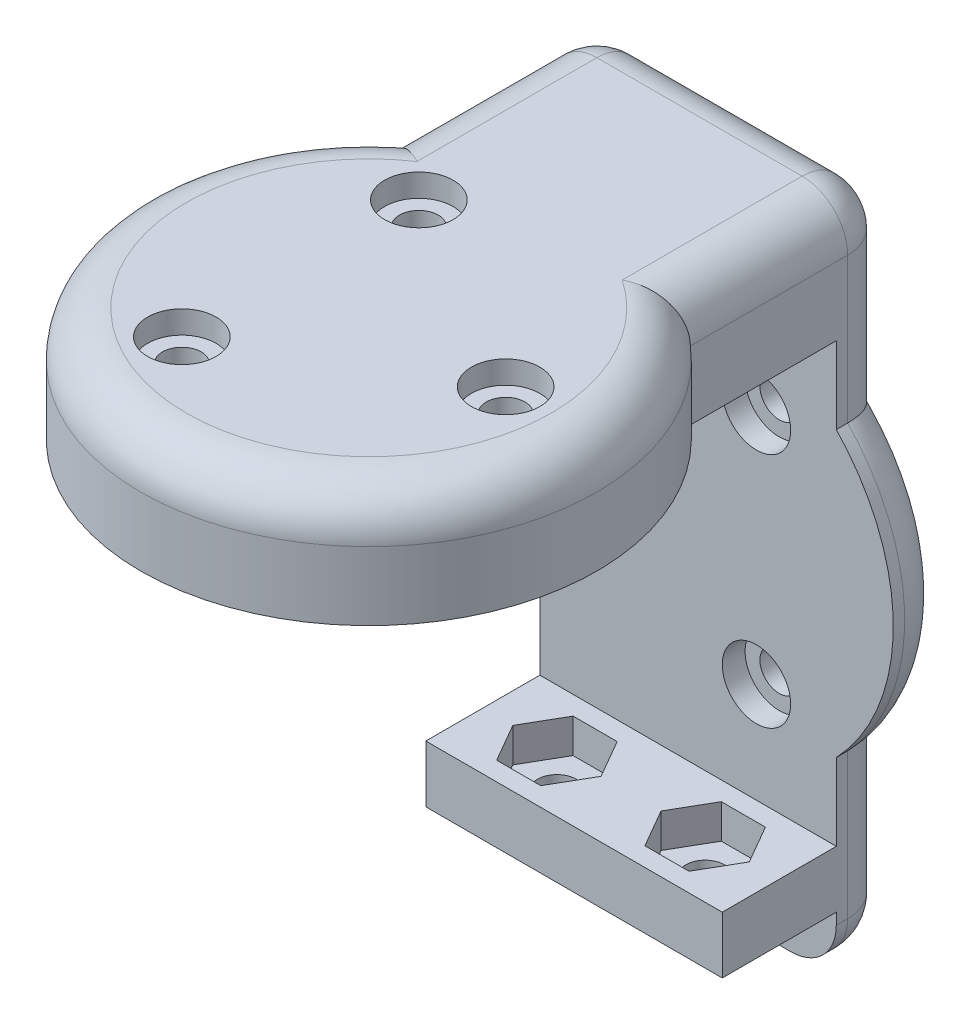
SolidWorks part; units mm, degrees
ref_plane "前视基准面" through (0, 0, 0) normal (0, 0, 1) x (1, 0, 0)
ref_plane "上视基准面" through (0, 0, 0) normal (0, 1, 0) x (1, 0, 0)
ref_plane "右视基准面" through (0, 0, 0) normal (1, 0, 0) x (0, 0, -1)
sketch "草图1" plane through (0, 0, 0) normal (0, 0, 1) x (1, 0, 0)
  line L0 (-6.5, -6.2249) -> (-6.5, -9.6)
  line L5 (-6.5, 9.6) -> (6.5, 9.6)
  line L6 (-6.5, 9.6) -> (-6.5, 6.2249)
  line L7 (-6.5, -9.6) -> (6.5, -9.6)
  line L8 (6.5, 9.6) -> (6.5, 6.2249)
  line L9 (6.5, -6.2249) -> (6.5, -9.6)
  arc A0 (-6.5, 6.2249) -> (-6.5, -6.2249) centre (0, 0) ccw
  arc A1 (6.5, -6.2249) -> (6.5, 6.2249) centre (0, 0) ccw
  point P0 (0, 0)
  point P1 (0, 0)
  point P20 (-2.9403, 5.0928)
  point P24 (-2.9182, -5.2425)
extrude "凸台-拉伸1" add sketch "草图1" along normal blind 2.5 contours L5 L8 A1 L9 L7 L0 A0 L6
ref_plane "基准面4" through (0, 0, -10) normal (0, 0, -1) x (-1, 0, 0)
sketch "草图2" plane through (0, 0, -10) normal (0, 0, -1) x (-1, 0, 0)
  line L1 (6.5, -9.6) -> (-6.5, -9.6)
  line L2 (6.5, -9.6) -> (6.5, -12.1)
  line L3 (6.5, -12.1) -> (-6.5, -12.1)
  line L4 (-6.5, -9.6) -> (-6.5, -12.1)
  circle A8 centre (6, 0) radius 0.85
  circle A9 centre (6, 0) radius 1.5
  circle A10 centre (-3, 5.1962) radius 0.85
  circle A11 centre (-3, 5.1962) radius 1.5
  circle A12 centre (-3, -5.1962) radius 0.85
  circle A13 centre (-3, -5.1962) radius 1.5
extrude "切除-拉伸1" cut sketch "草图2" against normal blind 16.5 contours A12 | A8 | A10
extrude "切除-拉伸2" cut sketch "草图2<3>" along normal blind 1 from surface contours A13 | A9 | A11 starting at face at (3.85, -5.1962, 2.5)
sketch "草图2<3>" plane through (0, 0, -10) normal (0, 0, -1) x (-1, 0, 0) same geometry as "草图2"
sketch "草图3" plane through (0, 0, 0) normal (0, 1, 0) x (1, 0, 0)
  line L1 (6.5, 0) -> (-6.5, 0)
  line L2 (6.5, 0) -> (6.5, -8.9007)
  line L4 (-6.5, 0) -> (-6.5, -8.9007)
  arc A0 (-6.5, -8.9007) -> (6.5, -8.9007) centre (0, -16.5) ccw
extrude "凸台-拉伸2" add sketch "草图3" along normal blind 5 from surface starting at face at (0, 9.6, 1.25)
ref_plane "基准面5" through (0, 24.6, 0) normal (0, 1, 0) x (1, 0, 0)
sketch "草图4" plane through (0, 24.6, 0) normal (0, 1, 0) x (1, 0, 0)
  line L16 (-6.5, 0) -> (6.5, 0)
  line L17 (-6.5, 0) -> (-6.5, -2.5)
  line L18 (-6.5, -2.5) -> (6.5, -2.5)
  line L19 (6.5, 0) -> (6.5, -2.5)
  line L20 (2.2829, -6.675) -> (1.3159, -5)
  line L21 (-1.3159, -5) -> (-2.2829, -3.325)
  line L22 (-2.2829, -3.325) -> (-4.2171, -3.325)
  line L23 (-4.2171, -3.325) -> (-5.1841, -5)
  line L24 (-5.1841, -5) -> (-4.2171, -6.675)
  line L25 (-4.2171, -6.675) -> (-2.2829, -6.675)
  line L26 (-2.2829, -6.675) -> (-1.3159, -5)
  line L27 (4.2171, -6.675) -> (2.2829, -6.675)
  line L28 (5.1841, -5) -> (4.2171, -6.675)
  line L29 (4.2171, -3.325) -> (5.1841, -5)
  line L30 (2.2829, -3.325) -> (4.2171, -3.325)
  line L31 (1.3159, -5) -> (2.2829, -3.325)
  circle A10 centre (0, -16.5) radius 8.5
  circle A11 centre (6, -16.5) radius 0.85
  circle A14 centre (6, -16.5) radius 1.5
  circle A15 centre (-3, -11.3038) radius 0.85
  circle A16 centre (-3, -11.3038) radius 1.5
  circle A17 centre (-3, -21.6962) radius 0.85
  circle A18 centre (-3, -21.6962) radius 1.5
  circle A19 centre (0, -16.5) radius 6.1
  circle A20 centre (-3.25, -5) radius 0.85
  circle A21 centre (-3.25, -5) radius 1.5
  circle A22 centre (-3.25, -5) radius 1.675 construction
  circle A23 centre (3.25, -5) radius 1.675 construction
  circle A24 centre (3.25, -5) radius 1.5
  circle A25 centre (3.25, -5) radius 0.85
  point P0 (0, -16.5)
extrude "切除-拉伸3" cut sketch "草图4" against normal blind 5 from surface contours A17 | A11 | A15 starting at face at (0, 14.6, 8.8502)
extrude "切除-拉伸4" cut sketch "草图4<3>" against normal blind 1 from surface contours A18 | A16 | A14 starting at face at (-3.85, 14.6, 21.6962)
sketch "草图4<3>" plane through (0, 24.6, 0) normal (0, 1, 0) x (1, 0, 0) same geometry as "草图4"
extrude "切除-拉伸5" cut sketch "草图4<4>" along normal blind 2.5 from surface contours A10 starting at face at (-3.85, 9.6, 21.6962)
sketch "草图4<4>" plane through (0, 24.6, 0) normal (0, 1, 0) x (1, 0, 0) same geometry as "草图4"
extrude "凸台-拉伸3" add sketch "草图4<5>" against normal blind 5 from surface contours L16 L19 L18 L17 starting at face at (0, -9.6, 1.25)
sketch "草图4<5>" plane through (0, 24.6, 0) normal (0, 1, 0) x (1, 0, 0) same geometry as "草图4"
extrude "凸台-拉伸4" add sketch "草图2<5>" against normal blind 5 from surface contours L1 L4 L3 L2 starting at face at (4.5, -5.1962, 2.5)
sketch "草图2<5>" plane through (0, 0, -10) normal (0, 0, -1) x (-1, 0, 0) same geometry as "草图2"
extrude "切除-拉伸6" cut sketch "草图4<7>" against normal blind 1.5 from surface contours L22 L23 L24 L25 L26 L21 | L30 L29 L28 L27 L20 L31 starting at face at (0, -9.6, 5)
sketch "草图4<7>" plane through (0, 24.6, 0) normal (0, 1, 0) x (1, 0, 0) same geometry as "草图4"
extrude "切除-拉伸7" cut sketch "草图4<8>" against normal blind 2.5 from surface contours A20 | A25 starting at face at (0, -9.6, 5)
sketch "草图4<8>" plane through (0, 24.6, 0) normal (0, 1, 0) x (1, 0, 0) same geometry as "草图4"
fillet "圆角1" radius 2 10 edges at (0, 14.6, 26.5) (-6.5, 14.6, 4.4503) (6.5, 14.6, 4.4503) (0, 14.6, 0) (-6.5, 10.4125, 0) (-9, 0, 0) (0, -14.6, 0) (6.5, -10.4125, 0) (9, 0, 0) (6.5, 10.4125, 0)
fillet "圆角2" radius 2 5 edges at (-6.5, -7.599, 0) (-6.5, -14.0142, 0.5858) (5.9142, -14.0142, 0.5858) (-6.5, -14.6, 2.25) (6.5, -14.6, 2.25)
